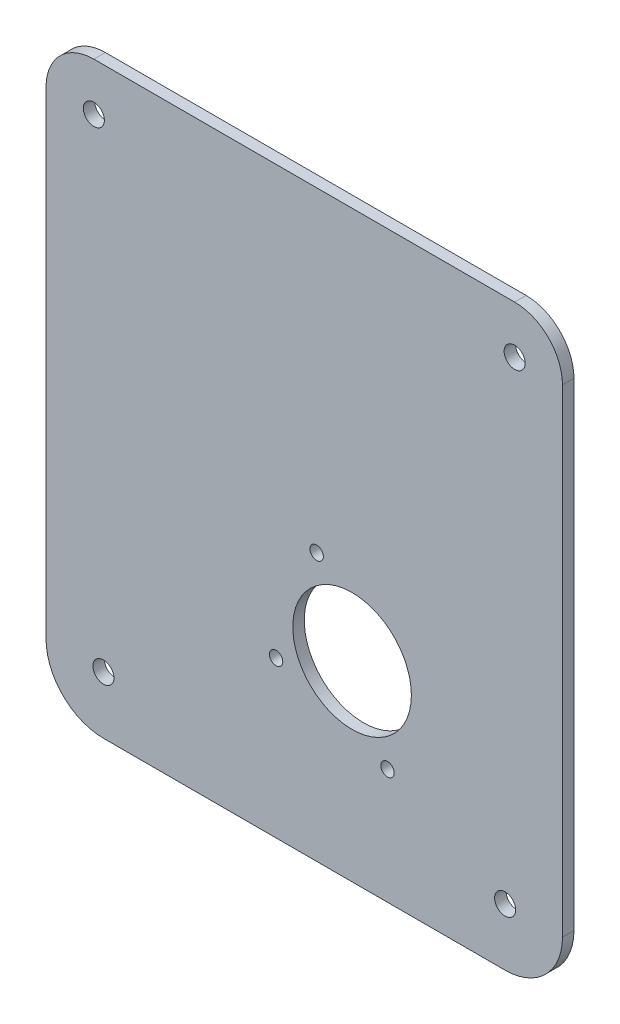
SolidWorks part; units mm, degrees
note: '?' marks a value the reader was unsure of.
other "Title Block Table1"
other "DetailItem1"
material "6082-T6 Aluminium"
ref_plane "Front Plane" through (0, 0, 0) normal (0, 0, 1) x (1, 0, 0)
ref_plane "Top Plane" through (0, 0, 0) normal (0, 1, 0) x (1, 0, 0)
ref_plane "Right Plane" through (0, 0, 0) normal (1, 0, 0) x (0, 0, -1)
ref_axis "X-Axis" through (-87.25, 0, 0) along (1, 0, 0)?
ref_axis "Y-Axis" through (0, 120.625, 0) along (0, -1, 0)?
ref_axis "Z-Axis" through (0, 0, -0.25) along (0, 0, 1)?
sketch "Sketch1" plane through (0, 0, 0) normal (0, 0, 1) x (1, 0, 0)
  line L0 (0, 0) -> (0, -50) construction
  line L2 (-80, 90) -> (-80, -50) construction
  line L3 (-80, -50) -> (80, -50) construction
  line L5 (-67.5, 102.5) -> (42.5, 102.5)
  line L6 (55, 90) -> (55, -35)
  line L8 (40, -50) -> (-65, -50)
  line L9 (-80, -35) -> (-80, 90)
  arc A0 (-67.5, 102.5) -> (-80, 90) centre (-67.5, 90) ccw
  arc A1 (55, -35) -> (40, -50) centre (40, -35) cw
  arc A2 (-65, -50) -> (-80, -35) centre (-65, -35) cw
  arc A3 (42.5, 102.5) -> (55, 90) centre (42.5, 90) cw
  point P0 (0, 0)
  dimension "D5" = 15
  dimension "D1" = 12.5
  dimension "D2" = 140
  dimension "D3" = 50
  dimension "D4" = 120
  dimension "D6" = 80
base flange "Base-Flange1" sketch "Sketch1" thickness 3 reverse thickness direction yes parameters "D1"=3
sketch "Sketch2" plane through (0, 0, 3) normal (0, 0, 1) x (1, 0, 0)
  line L0 (-65, -50) -> (40, -50) construction
  line L1 (-9.2639, 19.8665) -> (19.8665, 9.2639) construction
  line L2 (-9.2639, 19.8665) -> (-19.8665, -9.2639) construction
  line L3 (-19.8665, -9.2639) -> (9.2639, -19.8665) construction
  line L4 (19.8665, 9.2639) -> (9.2639, -19.8665) construction
  line L5 (-9.2639, 19.8665) -> (9.2639, -19.8665) construction
  line L6 (-19.8665, -9.2639) -> (19.8665, 9.2639) construction
  circle A0 centre (0, 0) radius 15.5
  circle A2 centre (-19.8665, -9.2639) radius 1.75
  circle A3 centre (9.2639, -19.8665) radius 1.75
  circle A5 centre (-9.2639, 19.8665) radius 1.75
  dimension "D1" = 31
  dimension "D3" = 3.5
  dimension "D2" = 31
  dimension "D4" = 20
extrude "Cut-Extrude1" cut sketch "Sketch2" against normal through all normal cut yes
hole_wizard "M5 Clearance Hole1" positions "Sketch3" profile "Sketch5" hole size "M5" standard "DIN" end condition through all
sketch "Sketch3" plane through (0, 0, 0) normal (0, 0, -1) x (-1, 0, 0)
  point P0 (-40, -35)
  point P3 (67.5, 90)
  point P6 (65, -35)
  point P9 (-42.5, 90)
sketch "Sketch5" plane through (40, -35, 0) normal (1, 0, 0) x (0, 1, 0)
  line L0 (0, 0) -> (0, 3)
  line L1 (0, 3) -> (2.75, 3)
  line L2 (2.75, 3) -> (2.75, 0)
  line L5 (2.75, 0) -> (0, 0)
  line L11 (0, -6.35) -> (0, 107.95) construction
  dimension "Thru Hole Dia." = 5.5
  dimension "Thru Hole Depth" = 3
sketch "Bend-Lines1" [suppressed] plane through (0, 0, 0) normal (0, 1, 0) x (1, 0, 0)
sketch "Bounding-Box1" [suppressed] plane through (0, 0, 0) normal (0, 1, 0) x (1, 0, 0)
sheet metal parameters "Sheet-Metal3" thickness 3 parameters "D1"=5
flat pattern "Flat-Pattern3" [suppressed]
sketch "Bend-Lines2" plane through (0, 0, 0) normal (0, 1, 0) x (1, 0, 0)
sketch3d "Bounding-Box2" [suppressed]
  line L0 (-73.324, -72.775, 0) -> (73.324, -72.775, 0) construction
  line L1 (-73.324, 72.775, 0) -> (73.324, 72.775, 0) construction
  line L2 (-73.324, -72.775, 0) -> (-73.324, 72.775, 0) construction
  line L3 (73.324, -72.775, 0) -> (73.324, 72.775, 0) construction
sheet metal parameters "Sheet-Metal4" thickness 3 parameters "D1"=5
flat pattern "Flat-Pattern3"
sketch "Bend-Lines2" plane through (0, 0, 0) normal (0, 1, 0) x (1, 0, 0)
sketch3d "Bounding-Box2" [suppressed]
  line L0 (-12.5, 196.7647, 0) -> (-12.5, -12.5, 0) construction
  line L1 (111.2472, 196.7647, 0) -> (111.2472, -12.5, 0) construction
  line L2 (-12.5, 196.7647, 0) -> (111.2472, 196.7647, 0) construction
  line L3 (-12.5, -12.5, 0) -> (111.2472, -12.5, 0) construction
sheet metal parameters "Sheet-Metal5" thickness 3 parameters "D1"=5
flat pattern "Flat-Pattern3"
sketch "Bend-Lines2" plane through (0, 0, 0) normal (0, 1, 0) x (1, 0, 0)
sketch3d "Bounding-Box2" [suppressed]
  line L0 (-132.5, -150, 0) -> (-132.5, 12.5, 0) construction
  line L1 (12.5, -150, 0) -> (12.5, 12.5, 0) construction
  line L2 (-132.5, -150, 0) -> (12.5, -150, 0) construction
  line L3 (-132.5, 12.5, 0) -> (12.5, 12.5, 0) construction
